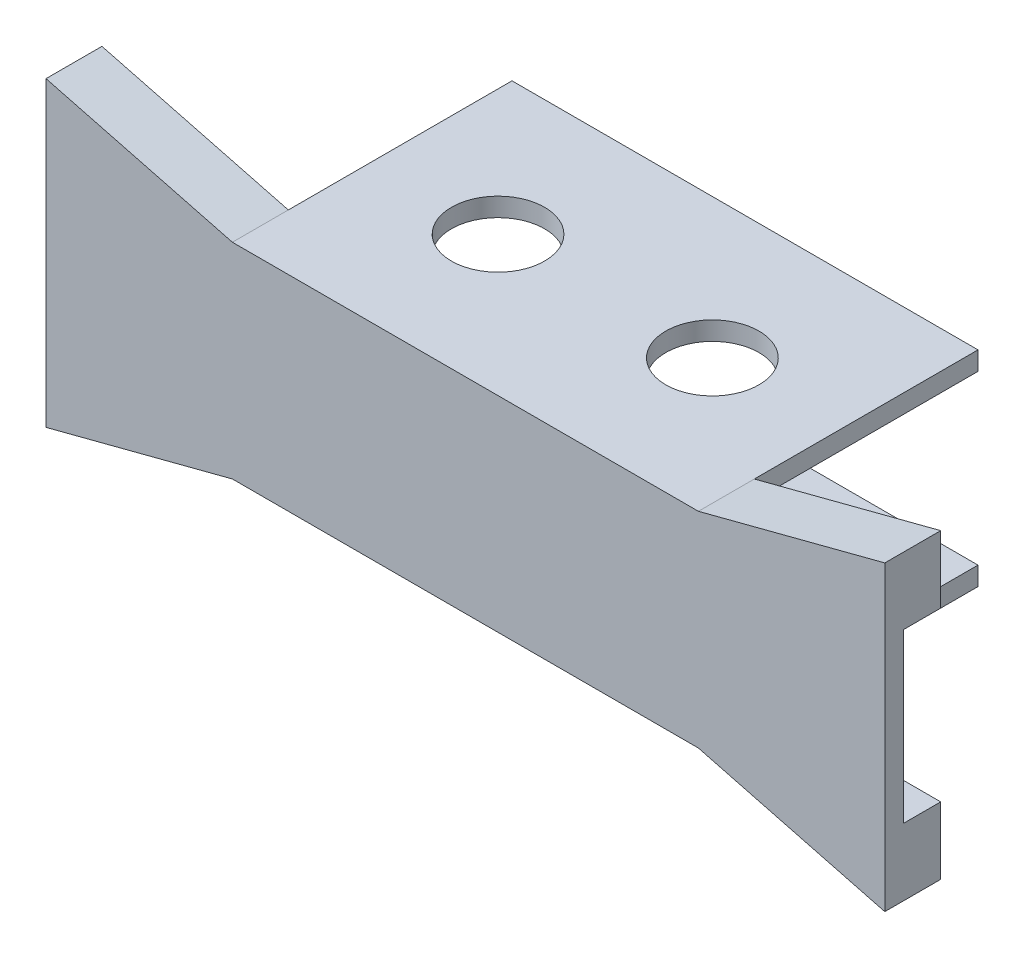
SolidWorks part; units mm, degrees
material "AISI 1020 Steel, Cold Rolled"
ref_plane "Front Plane" through (0, 0, 0) normal (0, 0, 1) x (1, 0, 0)
ref_plane "Top Plane" through (0, 0, 0) normal (0, 1, 0) x (1, 0, 0)
ref_plane "Right Plane" through (0, 0, 0) normal (1, 0, 0) x (0, 0, -1)
sketch "Sketch1" plane through (0, 0, 0) normal (0, 1, 0) x (1, 0, 0)
  line L0 (-18.8144, 15.9278) -> (-18.8144, -14.0722) construction
  line L1 (6.1856, -14.0722) -> (-43.8144, -14.0722)
  line L2 (6.1856, -14.0722) -> (6.1856, 15.9278)
  line L3 (6.1856, 15.9278) -> (-43.8144, 15.9278)
  line L4 (-43.8144, -14.0722) -> (-43.8144, 15.9278)
  line L5 (-7.3144, 0.9278) -> (-30.3144, 0.9278)
  circle A0 centre (-30.3144, 0.9278) radius 5
  circle A1 centre (-7.3144, 0.9278) radius 5
  point P9 (-18.8144, 0.9278)
  dimension "D1" = 30
  dimension "D2" = 50
extrude "Boss-Extrude2" add sketch "Sketch1" along normal blind 2 contours L3 L0 A1 L1 L2 | L0 L3 L4 L1 A0 region at (-6.3144, 0, -15.5373) region at (-19.2049, 0, -8.4278)
sketch "Sketch2" plane through (0, 0, 14.0722) normal (0, 0, 1) x (1, 0, 0)
  line L0 (-43.8144, 0) -> (-63.8144, 0)
  line L1 (6.1856, 0) -> (26.1856, 0)
  line L2 (-43.8144, 2) -> (-63.8144, 7.203)
  line L3 (-63.8144, 0) -> (26.1856, 0)
  line L4 (-63.8144, 0) -> (-63.8144, -9)
  line L5 (-63.8144, -9) -> (26.1856, -9)
  line L6 (26.1856, 0) -> (26.1856, -9)
  line L7 (-63.8144, 7.203) -> (-63.8144, 0)
  line L8 (6.1856, 2) -> (26.1856, 7.203)
  line L9 (26.1856, 7.203) -> (26.1856, 0)
  line L10 (-43.8144, 2) -> (-43.8144, 0)
  line L11 (6.1856, 2) -> (6.1856, 0)
  line M4 (-43.8144, 0) -> (6.1856, 0)
  line M5 (6.1856, 0) -> (6.1856, 2)
  line M7 (-43.8144, 2) -> (-43.8144, 0)
  dimension "D1" = 9
extrude "Boss-Extrude3" add sketch "Sketch2" against normal blind 2 contours L6 L1 L0 L4 L5 M4 region at (-18.8144, -4.5, 14.0722)
extrude "Boss-Extrude4" add sketch "Sketch2<4>" against normal blind 6 contours L9 L8 L1 M5 | L2 L7 L0 M7 region at (-55.699, 2.5459, 14.0722) region at (18.0701, 2.5459, 14.0722)
sketch "Sketch2<4>" plane through (0, 0, 14.0722) normal (0, 0, 1) x (1, 0, 0) same geometry as "Sketch2"
mirror "Mirror1" about plane through (0, -9, 12.0722) normal (0, -1, 0) of bodies 104
